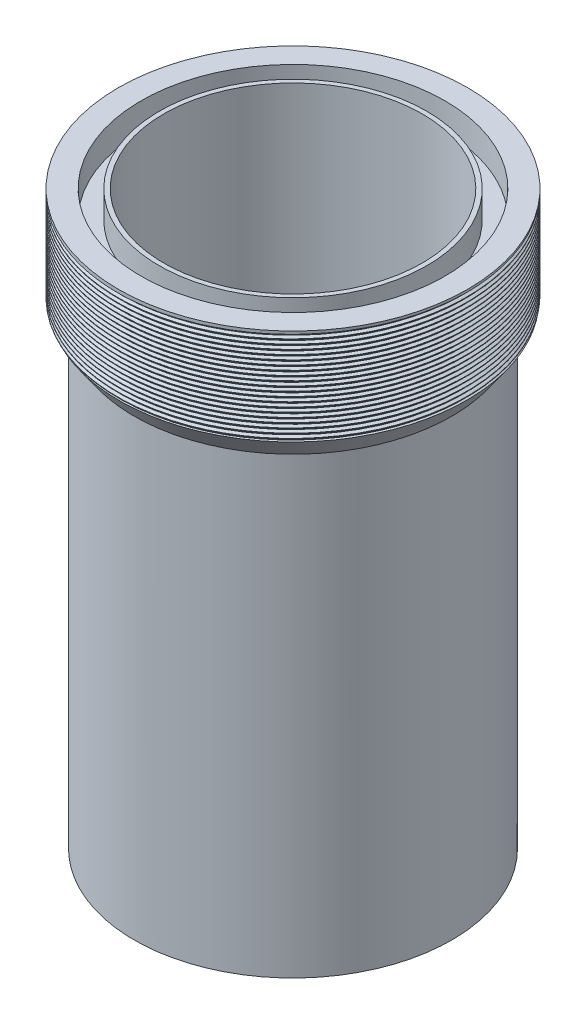
SolidWorks part; units mm, degrees
material "AISI 316 Annealed Stainless Steel Bar (SS)"
ref_plane "Front Plane" through (0, 0, 0) normal (0, 0, 1) x (1, 0, 0)
ref_plane "Top Plane" through (0, 0, 0) normal (0, 1, 0) x (1, 0, 0)
ref_plane "Right Plane" through (0, 0, 0) normal (1, 0, 0) x (0, 0, -1)
sketch "Sketch1" plane through (0, 0, 0) normal (0, 0, 1) x (1, 0, 0)
  line L0 (0, 0) -> (28.5, 0)
  line L1 (28.5, 0) -> (28.5, 118)
  line L2 (28.5, 118) -> (29.5, 118)
  line L3 (38.5, 118) -> (38.5, 97)
  line L4 (38.5, 97) -> (35, 92)
  line L5 (35, 92) -> (35, -8)
  line L6 (35, -8) -> (0, -8)
  line L7 (0, -8) -> (0, 0)
  line L8 (0, 0) -> (0, 83.8579) construction
  line L9 (29.5, 118) -> (29.5, 112)
  line L10 (29.5, 112) -> (33.5, 112)
  line L11 (33.5, 112) -> (33.5, 118)
  line L12 (33.5, 118) -> (38.5, 118)
  dimension "D1" = 118
  dimension "D2" = 10
  dimension "D3" = 21
  dimension "D4" = 35
  dimension "D5" = 28.5
  dimension "D6" = 100
  dimension "D7" = 8
  dimension "D8" = 1
  dimension "D9" = 6
  dimension "D10" = 5
  dimension "D11" = 4
revolve "Revolve1" add sketch "Sketch1" angle 360 about L8
thread "Thread2" pitch 1 method cut profile "Thread Profile2" start angle 0, offset 0, length 0, pitch 1, diameter 77
ref_plane "Plane2" through (-38.5, 118, 0) normal (0, 0, 1) x (-1, 0, 0)
sketch "Thread Profile2" plane through (-38.5, 118, 0) normal (0, 0, 1) x (-1, 0, 0)
  line L0 (0, 0) -> (0, 1) construction
  line L11 (0, 0) -> (0, 0.875)
  line L12 (0, 0.875) -> (-0.5413, 0.5625)
  line L13 (-0.5413, 0.5625) -> (-0.5413, 0.3125)
  line L15 (-0.5413, 0.3125) -> (0, 0)
  line L17 (-0.5413, 0.4375) -> (0, 0.4375) construction
  point P2 (0, 0)
  dimension "Pitch" = 1
  dimension "Profile_Angle" = 60
  dimension "Profile_Land" = 0.25
  dimension "Profile_Height" = 0.5413
ref_axis "Axis1" through (0, 142.2097, 0) along (0, -1, 0)
